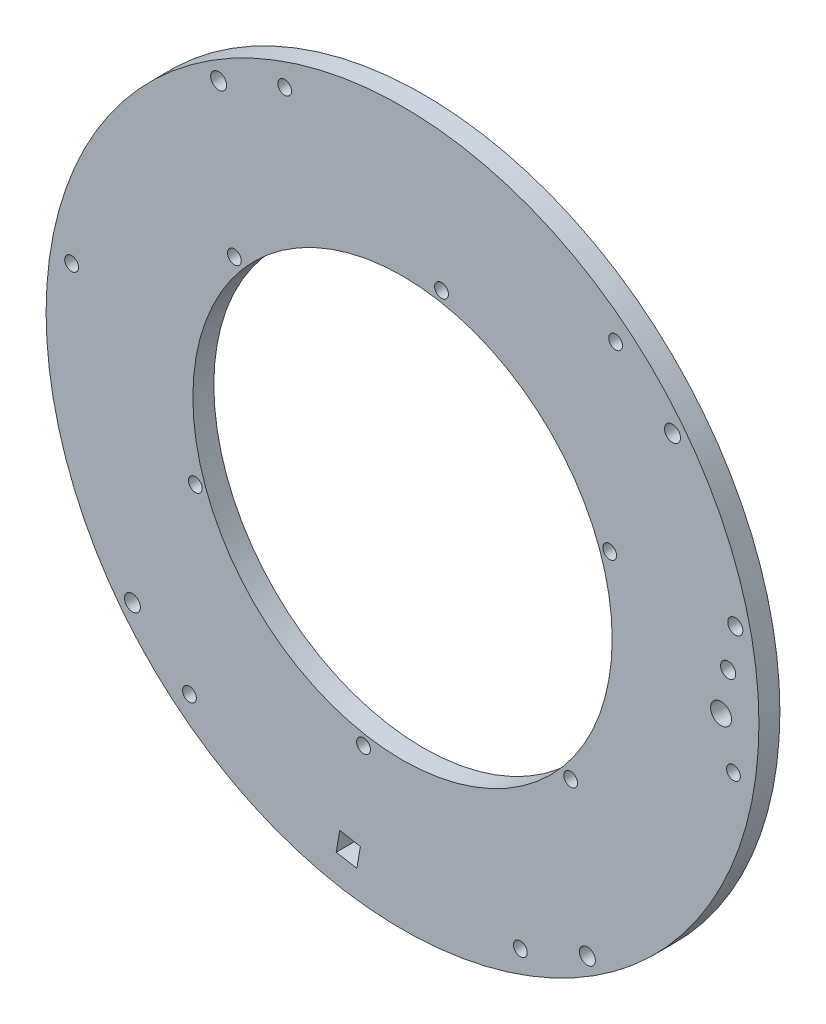
SolidWorks part; units mm, degrees
ref_plane "Front Plane" through (0, 0, 0) normal (0, 0, 1) x (1, 0, 0)
ref_plane "Top Plane" through (0, 0, 0) normal (0, 1, 0) x (1, 0, 0)
ref_plane "Right Plane" through (0, 0, 0) normal (1, 0, 0) x (0, 0, -1)
sketch "Sketch1" plane through (0, 0, 0) normal (0, 0, 1) x (1, 0, 0)
  circle A0 centre (51.7384, 55.5933) radius 107.95
  circle A1 centre (51.7384, 55.5933) radius 63.5
extrude "Boss-Extrude1" add sketch "Sketch1" along normal blind 6.35
sketch "Sketch3" plane through (0, 0, 6.35) normal (0, 0, 1) x (1, 0, 0)
  circle A0 centre (-12.7986, -22.8767) radius 2.085 construction
  circle A1 centre (-12.7986, -22.8767) radius 2.085
extrude "Cut-Extrude2" cut sketch "Sketch3" against normal through all
pattern_circular "CirPattern1" count 6 every 60 about axis through (51.7384, 55.5933, 6.35) along (0, 0, -1) of "Cut-Extrude2"
sketch "Sketch4" plane through (0, 0, 6.35) normal (0, 0, 1) x (1, 0, 0)
  circle A0 centre (39.9231, -10.0264) radius 2.085 construction
  circle A1 centre (39.9231, -10.0264) radius 2.085
extrude "Cut-Extrude3" cut sketch "Sketch4" against normal through all and the other way through all
pattern_circular "CirPattern2" count 6 every 60 about axis through (51.7384, 55.5933, 6.35) along (0, 0, -1) of "Cut-Extrude3"
sketch "Sketch5" plane through (0, 0, 6.35) normal (0, 0, 1) x (1, 0, 0)
  line L1 (-28.0129, -9.7969) -> (-27.3994, -6.2427) construction
  line L3 (-32.226, -9.5852) -> (-28.6717, -10.1987) construction
  line L6 (105.0238, -32.762) -> (105.6374, -29.2077) construction
  line L7 (109.1872, -33.9961) -> (105.6329, -33.3826) construction
  circle A0 centre (-30.0667, -7.5092) radius 2.413
  circle A1 centre (107.7257, -31.2952) radius 2.413
extrude "Cut-Extrude4" cut sketch "Sketch5" against normal through all
ref_plane "Plane1" through (31.651, -42.1086, -19.05) normal (0.1701, 0.9854, 0) x (0.9854, -0.1701, 0)
sketch "Sketch8" plane through (0, 0, 6.35) normal (0, 0, 1) x (1, 0, 0)
  line L4 (31.651, -42.1086) -> (32.7311, -35.8512)
  line L5 (32.7311, -35.8512) -> (38.9886, -36.9313)
  line L6 (38.9886, -36.9313) -> (37.9084, -43.1888)
  line L7 (37.9084, -43.1888) -> (31.651, -42.1086)
extrude "Cut-Extrude7" cut sketch "Sketch8" against normal through all both and the other way through all
sketch "Sketch9" plane through (0, 0, 6.35) normal (0, 0, 1) x (1, 0, 0)
  line L4 (130.8478, 117.4342) -> (131.4614, 120.9885) construction
  line L5 (131.8816, 121.4314) -> (135.4358, 120.8179) construction
  line L6 (-6.6159, 141.1634) -> (-6.0024, 144.7177) construction
  line L7 (-5.4154, 145.1319) -> (-1.8611, 144.5183) construction
  circle A0 centre (-3.9486, 142.43) radius 2.413
  circle A1 centre (133.5152, 118.7008) radius 2.413
extrude "Cut-Extrude8" cut sketch "Sketch9" against normal through all
sketch "Sketch10" plane through (0, 0, 0) normal (0, 0, -1) x (-1, 0, 0)
  line L0 (-148.2108, 52.5623) -> (-152.5315, 77.5921) construction
  circle A1 centre (-51.7384, 55.5933) radius 107.95
  circle A2 centre (-51.7384, 55.5933) radius 107.95
  circle A4 centre (-51.7384, 55.5933) radius 95.25 construction
  circle A9 centre (-148.2108, 52.5623) radius 3.175
  circle A10 centre (-150.3711, 65.0772) radius 2.286
  circle A11 centre (-152.5315, 77.5921) radius 2.286
  dimension "D1" = 0
extrude "Cut-Extrude10" cut sketch "Sketch10" against normal through all and the other way through all flip side to cut body kept at (159.6884, 55.5933, 0)
